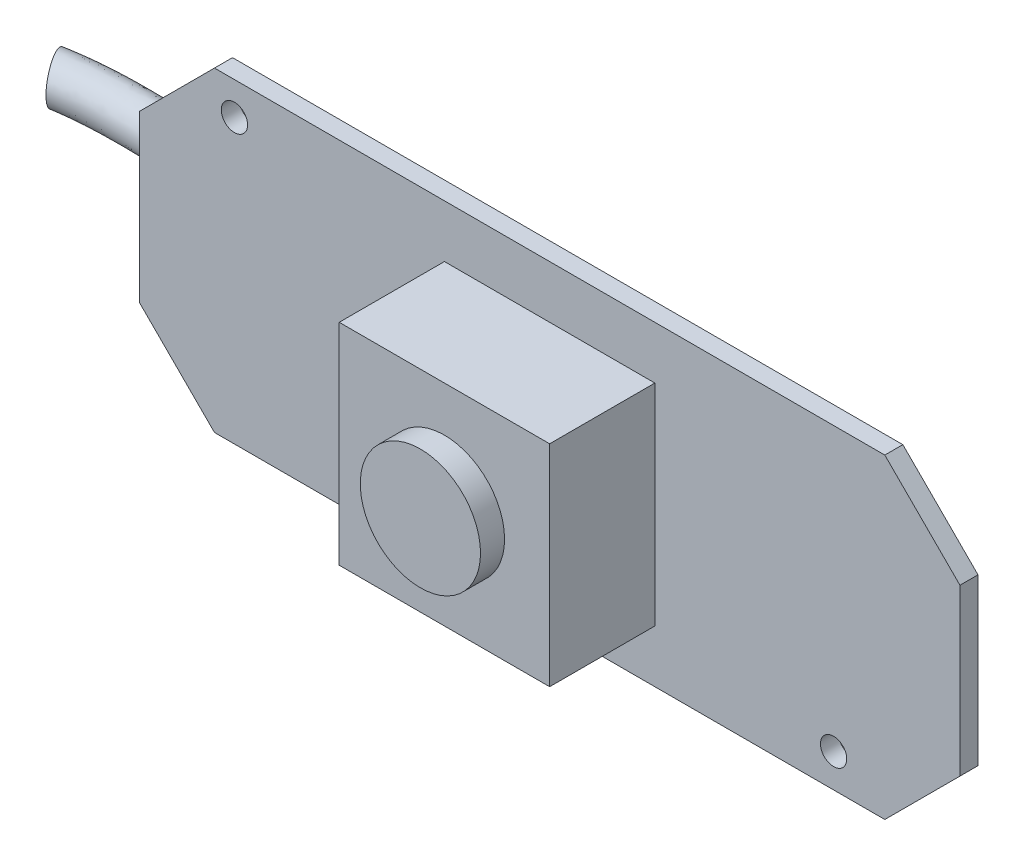
SolidWorks part; units mm, degrees
ref_plane "Front Plane" through (0, 0, 0) normal (0, 0, 1) x (1, 0, 0)
ref_plane "Top Plane" through (0, 0, 0) normal (0, 1, 0) x (1, 0, 0)
ref_plane "Right Plane" through (0, 0, 0) normal (1, 0, 0) x (0, 0, -1)
sketch "Sketch1" plane through (0, 0, 0) normal (0, 0, 1) x (1, 0, 0)
  line L0 (-22.3, 10.5) -> (-27.3, 5.5)
  line L1 (22.3, 10.5) -> (-22.3, 10.5)
  line L2 (27.3, 5.5) -> (27.3, -5.5)
  line L3 (22.3, -10.5) -> (-22.3, -10.5)
  line L4 (-27.3, 5.5) -> (-27.3, -5.5)
  line L5 (27.3, 10.5) -> (-27.3, -10.5) construction
  line L6 (27.3, -10.5) -> (-27.3, 10.5) construction
  line L7 (-27.3, -5.5) -> (-22.3, -10.5)
  line L8 (27.3, 5.5) -> (22.3, 10.5)
  line L9 (27.3, -5.5) -> (22.3, -10.5)
  line L10 (0, -11.55) -> (0, 11.55) construction
  line L11 (-27.3, 0) -> (27.3, 0) construction
  circle A0 centre (18.8914, -8.28) radius 0.875
  circle A1 centre (-18.8914, -8.28) radius 0.875 construction
  circle A2 centre (-18.8914, 8.28) radius 0.875 construction
  circle A3 centre (-20.9728, 8.32) radius 0.875
  point P0 (0, 0)
  dimension "D3" = 1.75
  dimension "D1" = 21
  dimension "D2" = 54.6
  dimension "D4" = 2.22
  dimension "D9" = 3.98
  dimension "D10" = 2.18
  dimension "D11" = 2.48
extrude "Boss-Extrude1" add sketch "Sketch1" along normal blind 1.2
sketch "Sketch2" plane through (0, 0, 1.2) normal (0, 0, 1) x (1, 0, 0)
  line L1 (7, 7) -> (-7, 7)
  line L2 (7, 7) -> (7, -7)
  line L3 (7, -7) -> (-7, -7)
  line L4 (-7, 7) -> (-7, -7)
  line L5 (7, 7) -> (-7, -7) construction
  line L6 (7, -7) -> (-7, 7) construction
  point P0 (0, 0)
  dimension "D1" = 14
extrude "Boss-Extrude2" add sketch "Sketch2" along normal blind 7
sketch "Sketch3" plane through (0, 0, 8.2) normal (0, 0, 1) x (1, 0, 0)
  circle A0 centre (0, 0) radius 4
  dimension "D1" = 8
extrude "Boss-Extrude3" add sketch "Sketch3" along normal blind 1.6
sketch "Sketch5" plane through (0, 0, 0) normal (0, 0, -1) x (-1, 0, 0)
  circle A0 centre (0, 0) radius 1.5
  dimension "D1" = 3
sketch3d "3DSketch1"
  spline S0 degree 3 poles (0, 0, 0) (1.1046, 0, -3.5439) (-5.5703, 0, -4.4766) (-11.6603, 0, -4.17) (-17.4003, 0, -4.176) (-25.9982, 0, -3.0777) (-32.7428, 0, -4.2755) (-37.514, 0, -3.4597) knots 0 0 0 0 0.218358 0.347455 0.497824 0.639134 1 1 1 1
sweep "Sweep1" add profiles "Sketch5" path "3DSketch1"
